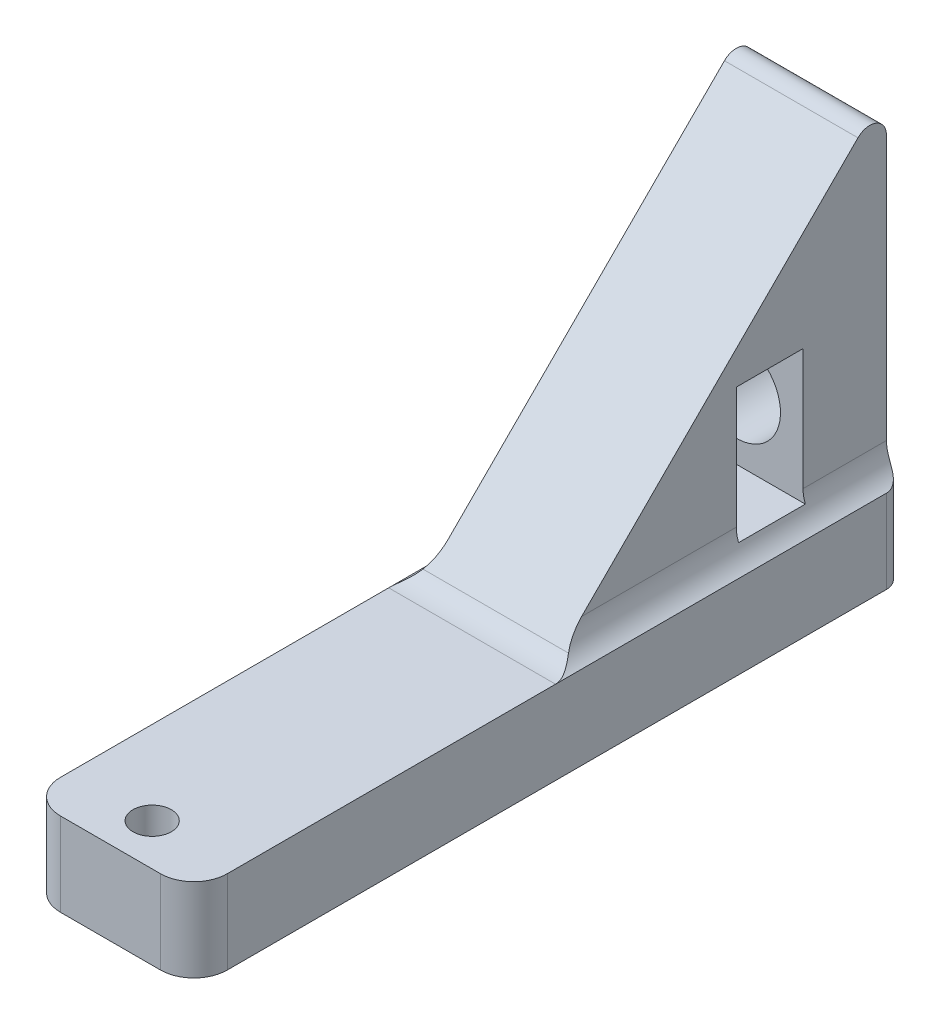
SolidWorks part; units mm, degrees
ref_plane "Front Plane" through (0, 0, 0) normal (0, 0, 1) x (1, 0, 0)
ref_plane "Top Plane" through (0, 0, 0) normal (0, 1, 0) x (1, 0, 0)
ref_plane "Right Plane" through (0, 0, 0) normal (1, 0, 0) x (0, 0, -1)
sketch "Sketch2" plane through (0, 0, 0) normal (0, 1, 0) x (1, 0, 0)
  line L1 (0, 0) -> (10, 0)
  line L2 (0, 0) -> (0, -42.5)
  line L3 (0, -42.5) -> (10, -42.5)
  line L4 (10, 0) -> (10, -42.5)
  circle A0 centre (5, -40) radius 1.15
  dimension "D3" = 2.3
  dimension "D1" = 42.5
  dimension "D2" = 10
  dimension "D4" = 5
  dimension "D5" = 2.5
extrude "Boss-Extrude1" add sketch "Sketch2" along normal blind 5
ref_plane "Plane1" through (5, 0, 0) normal (1, 0, 0) x (0, 0, -1)
sketch "Sketch3" plane through (5, 0, 0) normal (1, 0, 0) x (0, 0, -1)
  line L0 (0, 5) -> (-20, 5)
  line L1 (-42.5, 5) -> (0, 5) construction
  line L2 (-20, 5) -> (0, 25)
  line L3 (0, 25) -> (0, 5)
  dimension "D1" = 20
  dimension "D2" = 20
extrude "Boss-Extrude2" add sketch "Sketch3" along normal blind 4 and the other way blind 4
sketch "Sketch4" plane through (0, 0, 0) normal (0, 0, -1) x (-1, 0, 0)
  line L0 (-5, 2.75) -> (-5, -2.75) construction
  line L1 (-10, 0) -> (0, 0) construction
  circle A0 centre (-5, 10) radius 2.65
  dimension "D1" = 5.3
  dimension "D2" = 10
extrude "Cut-Extrude1" cut sketch "Sketch4" against normal blind 12
sketch "Sketch5" plane through (9, 0, 0) normal (1, 0, 0) x (0, 0, -1)
  line L0 (-42.5, 0) -> (0, 0) construction
  line L1 (-9, 14) -> (-5, 14)
  line L2 (-9, 14) -> (-9, 6)
  line L3 (-9, 6) -> (-5, 6)
  line L4 (-5, 14) -> (-5, 6)
  line L5 (0, 5) -> (0, 25) construction
  dimension "D1" = 8
  dimension "D2" = 4
  dimension "D3" = 6
  dimension "D4" = 5
extrude "Cut-Extrude2" cut sketch "Sketch5" against normal through all
fillet "Fillet1" radius 2 5 edges at (1, 5, 10) (9, 5, 10) (0, 2.5, 42.5) (10, 2.5, 42.5) (5, 5, 20)
fillet "Fillet2" radius 1 3 edges at (0, 2.5, 0) (10, 2.5, 0) (5, 25, 0)
equation "\"D4@Sketch2\"=\"D2@Sketch2\"/2"
